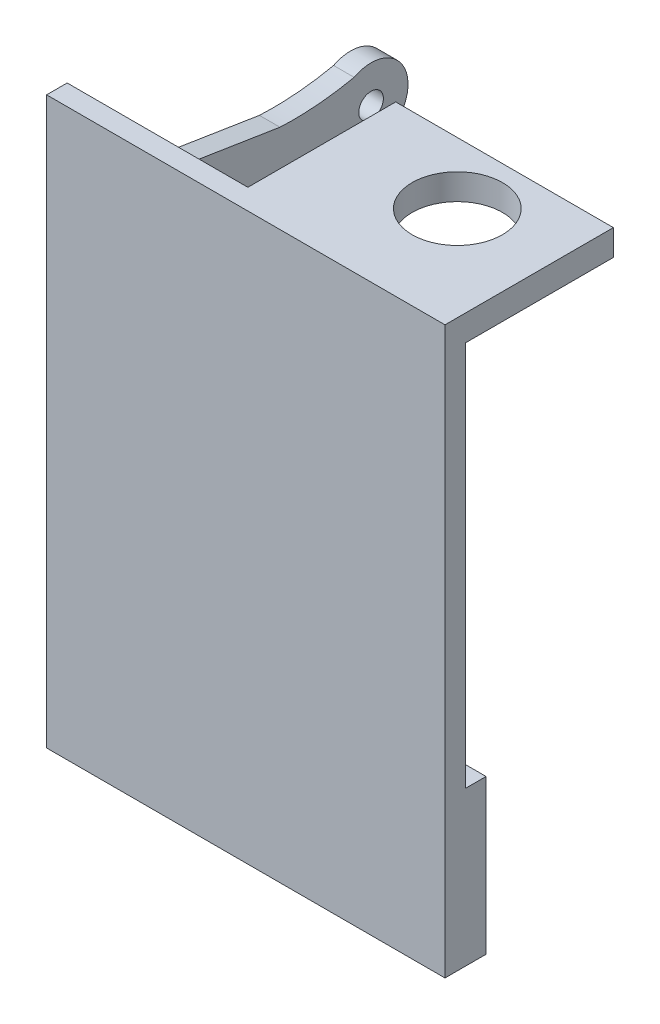
SolidWorks part; units mm, degrees
ref_plane "Plan de face" through (0, 0, 0) normal (0, 0, 1) x (1, 0, 0)
ref_plane "Plan de dessus" through (0, 0, 0) normal (0, 1, 0) x (1, 0, 0)
ref_plane "Plan de droite" through (0, 0, 0) normal (1, 0, 0) x (0, 0, -1)
sketch "Esquisse4" plane through (0, 0, 0) normal (0, 0, 1) x (1, 0, 0)
  line L1 (-23.5, 18.75) -> (23.5, 18.75)
  line L2 (-23.5, 18.75) -> (-23.5, -18.75)
  line L3 (-23.5, -18.75) -> (23.5, -18.75)
  line L4 (23.5, 18.75) -> (23.5, -18.75)
  line L5 (-23.5, 18.75) -> (23.5, -18.75) construction
  line L6 (-23.5, -18.75) -> (23.5, 18.75) construction
  point P0 (0, 0)
  dimension "D1" = 37.5
  dimension "D2" = 47
extrude "Boss.-Extru.2" add sketch "Esquisse4" along normal blind 10 contours L2 L3 L4 L1
sketch "Esquisse5" plane through (0, 0, 0) normal (0, 0, -1) x (-1, 0, 0)
  line L1 (-21.5, 16.75) -> (21.5, 16.75)
  line L2 (-21.5, 16.75) -> (-21.5, -16.75)
  line L3 (-21.5, -16.75) -> (21.5, -16.75)
  line L4 (21.5, 16.75) -> (21.5, -16.75)
  line L5 (-21.5, 16.75) -> (21.5, -16.75) construction
  line L6 (-21.5, -16.75) -> (21.5, 16.75) construction
  point P0 (0, 0)
  dimension "D1" = 43
  dimension "D2" = 33.5
extrude "Enlèv. mat.-Extru.1" cut sketch "Esquisse5" against normal blind 8
sketch "Esquisse6" plane through (0, -18.75, 0) normal (0, -1, 0) x (-1, 0, 0)
  line L0 (-23.5, -10) -> (-23.5, 0) construction
  line L1 (23.5, -10) -> (-23.5, -10)
  line L2 (23.5, -10) -> (23.5, -5)
  line L3 (23.5, -5) -> (-23.5, -5)
  line L4 (-23.5, -10) -> (-23.5, -5)
  dimension "D1" = 5
extrude "Boss.-Extru.3" add sketch "Esquisse6" against normal blind 137.74
sketch "Esquisse7" plane through (-23.5, 0, 0) normal (-1, 0, 0) x (0, 0, 1)
  line L1 (5, 118.99) -> (10, 118.99)
  line L2 (5, 118.99) -> (5, -18.75)
  line L3 (5, -18.75) -> (10, -18.75)
  line L4 (10, 118.99) -> (10, -18.75)
extrude "Boss.-Extru.4" add sketch "Esquisse7" along normal blind 50
sketch "Esquisse8" plane through (0, 0, 5) normal (0, 0, -1) x (-1, 0, 0)
  line L1 (73.5, 118.99) -> (34.1078, 118.99)
  line L2 (73.5, 118.99) -> (73.5, 41.3297)
  line L3 (73.5, 41.3297) -> (34.1078, 41.3297)
  line L4 (34.1078, 118.99) -> (34.1078, 41.3297)
  line L5 (-23.5, 118.99) -> (29.5, 118.99)
  line L6 (-23.5, 118.99) -> (-23.5, 112.69)
  line L7 (-23.5, 112.69) -> (29.5, 112.69)
  line L8 (29.5, 118.99) -> (29.5, 112.69)
  dimension "D1" = 53
  dimension "D2" = 6.3
extrude "Boss.-Extru.5" add sketch "Esquisse8" along normal blind 36 contours L6 L5 L8 L7
sketch "Esquisse9" plane through (0, 118.99, 0) normal (0, 1, 0) x (1, 0, 0)
  line L0 (23.5, 31) -> (-29.5, 31) construction
  line L1 (23.5, 31) -> (23.5, -10) construction
  circle A0 centre (0.5, 16) radius 11
  dimension "D1" = 15
  dimension "D2" = 23
extrude "Enlèv. mat.-Extru.4" cut sketch "Esquisse9" against normal blind 19 contours A0
sketch "Esquisse11" plane through (0, 0, 5) normal (0, 0, -1) x (-1, 0, 0)
  line L0 (73.5, 118.99) -> (29.5, 118.99) construction
  line L1 (73.5, 118.99) -> (68.5, 118.99)
  line L2 (73.5, 118.99) -> (73.5, 45.49)
  line L3 (73.5, 45.49) -> (68.5, 45.49)
  line L4 (68.5, 118.99) -> (68.5, 45.49)
  line L5 (73.5, 118.99) -> (73.5, -18.75) construction
  dimension "D1" = 73.5
  dimension "D2" = 5
extrude "Boss.-Extru.6" add sketch "Esquisse11" along normal blind 80
sketch "Esquisse12" plane through (-73.5, 0, 0) normal (-1, 0, 0) x (0, 0, 1)
  line L0 (-75, 45.49) -> (-75, 118.99) construction
  line L1 (10, 118.99) -> (-75, 118.99) construction
  circle A0 centre (-64, 82.24) radius 3
  dimension "D3" = 6
  dimension "D1" = 11
  dimension "D2" = 36.75
extrude "Enlèv. mat.-Extru.5" cut sketch "Esquisse12" against normal blind 70 contours A0
sketch "Esquisse16" plane through (-73.5, 0, 0) normal (-1, 0, 0) x (0, 0, 1)
  line L0 (-64.623, 79.3054) -> (10, 71.7945)
  line L1 (10, -18.75) -> (10, 118.99) construction
  line L2 (-64.0805, 85.2389) -> (10, 96.9471)
  line L3 (5, 45.49) -> (10, 45.49)
  line L4 (5, 45.49) -> (5, 118.99)
  line L5 (10, 118.99) -> (-75, 118.99) construction
  line L6 (-64, 82.24) -> (-75, 81.98)
  line L7 (-75, 45.49) -> (-75, 118.99) construction
  line L8 (-64.623, 79.3054) -> (-64.623, 73.2616)
  line L9 (-64.0805, 85.2389) -> (-64, 91.24)
  line L10 (-27.0402, 91.093) -> (-27.3115, 75.5499)
  circle A0 centre (-64, 82.24) radius 9
  circle A1 centre (-64, 82.24) radius 3 construction
  spline S0 degree 2 poles (-64.623, 73.2616) (-46.1218, 79.3481) (-27.3115, 75.5499) knots 0 0 0 1 1 1
  spline S1 degree 2 poles (-64, 91.24) (-45.4071, 86.1849) (-27.0402, 91.093) knots 0 0 0 1 1 1
  line M3 (10, 118.99) -> (-75, 118.99)
  line M4 (-75, 118.99) -> (-75, 45.49)
  line M5 (-75, 45.49) -> (5, 45.49)
  dimension "D1" = 75
  dimension "D2" = 75
extrude "Enlèv. mat.-Extru.6" cut sketch "Esquisse16" against normal blind 10 contours A0 L4 M3 M4 | A0 L4 M4 M5 region at (-73.5, 60.3969, -35.7954) region at (-73.5, 104.8624, -36.8977)
